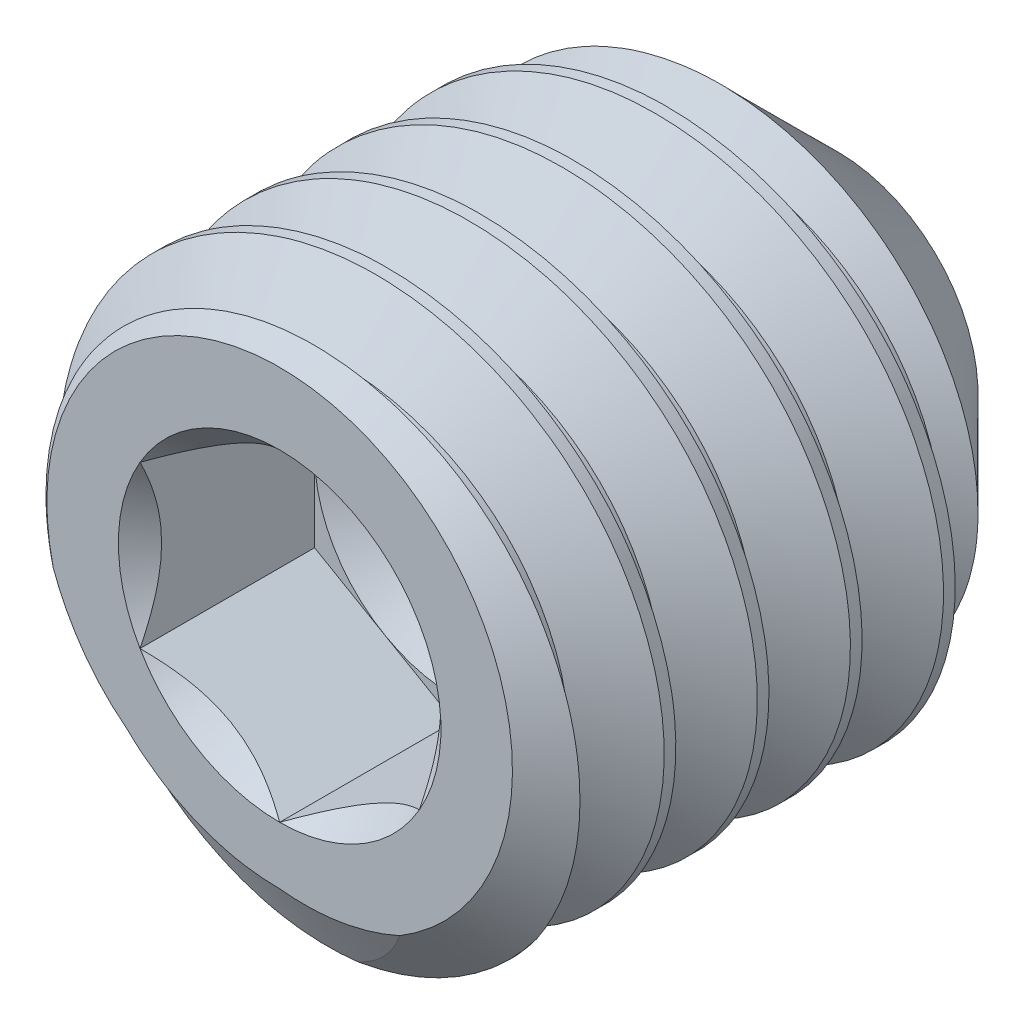
SolidWorks part; units mm, degrees
other "Imported1" parameters "D3"=3.3, "D1"=46.842, "Length"=3, "Drive Size"=1.5, "Thread Size"=3, "Thread Pitch"=0.5, "D2"=0.0866, "hex Depth"=0.9375, "Dia"=12, "D4"=2.3829, "Cup Point Dia"=3.3528, "D5"=1.436, "D6"=1.4986, "D7"=5.0014, "Pitch"=1.75
ref_plane "Front" through (0, 0, 0) normal (0, 0, 1) x (1, 0, 0)
ref_plane "Top" through (0, 0, 0) normal (0, 1, 0) x (1, 0, 0)
ref_plane "Right" through (0, 0, 0) normal (1, 0, 0) x (0, 0, -1)
sketch "Sketch1" plane through (0, 0, 0) normal (1, 0, 0) x (0, 0, -1)
  line L0 (1.5, 1.5) -> (-1.5, 1.5) construction
  line L1 (-1.5, 1.5) -> (-1.5, -1.5) construction
  line L2 (-1.5, -1.5) -> (1.5, -1.5) construction
  line L3 (1.5, -1.5) -> (1.5, 1.5) construction
  line L4 (-1.5, 0.75) -> (-1.5, -0.75) construction
  line L5 (1.4688, 1.5541) -> (1.9688, 1.5541) construction
  line L6 (1.4688, 1.5541) -> (1.5, 1.5) construction
  line L7 (1.5, 1.5) -> (1.9375, 1.5) construction
  line L8 (1.9375, 1.5) -> (1.9688, 1.5541) construction
  line L9 (1.5, 1.5) -> (1.7188, 1.1211) construction
  line L10 (1.7188, 1.1211) -> (1.9375, 1.5) construction
  line L11 (1.6875, 1.1752) -> (1.75, 1.1752) construction
  line L12 (1.7188, 1.5541) -> (1.7188, 1.5) construction
  line L13 (1.7188, 1.1752) -> (1.7188, 1.1211) construction
  point P3 (0, 1.5)
  point P24 (-1.5, 0)
  point P25 (-1.5, 0)
  dimension "D1" = 0.0625
sketch "Sketch11" plane through (0, 0, 0) normal (1, 0, 0) x (0, 0, -1)
  line L0 (-1.5, 0) -> (-1.5, 1.25)
  line L1 (-1.5, 1.25) -> (-1.3249, 1.5)
  line L2 (-1.3249, 1.5) -> (0.75, 1.5)
  line L3 (0.75, 1.5) -> (1.5, 0.75)
  line L4 (1.5, 0.75) -> (1.0494, 0)
  line L5 (1.0494, 0) -> (-1.5, 0)
  line L6 (1.0494, 0) -> (1.5, 0) construction
  line L7 (1.5, 0) -> (1.5, 0.75) construction
  line L8 (1.5, -0.75) -> (1.0494, 0) construction
  line L9 (-1.3249, -1.5) -> (0.75, -1.5) construction
  line L10 (-1.5, -1.5) -> (1.5, -1.5) construction
  line L11 (-1.5, 1.5) -> (-1.5, -1.5) construction
  line L12 (1.5, -1.5) -> (1.5, 1.5) construction
  point P11 (-0.25, -1.5)
  point P12 (-1.5, 1.5)
  dimension "D3" = 35
  dimension "D5" = 118
  dimension "D6" = 45
  dimension "D1" = 0.25
  dimension "D2" = 1.75
  dimension "D4" = 0.75
revolve "Revolve1" add sketch "Sketch11" angle 360 about L6
sketch "Sketch2" plane through (0, 0, 1.5) normal (0, 0, 1) x (1, 0, 0)
  line L1 (0, 0.866) -> (-0.75, 0.433)
  line L2 (-0.75, 0.433) -> (-0.75, -0.433)
  line L3 (-0.75, -0.433) -> (0, -0.866)
  line L4 (0, -0.866) -> (0.75, -0.433)
  line L5 (0.75, -0.433) -> (0.75, 0.433)
  line L6 (0.75, 0.433) -> (0, 0.866)
  circle A0 centre (0, 0) radius 0.75 construction
  circle A1 centre (0, 0) radius 1.5 construction
extrude "Cut-Extrude1" cut sketch "Sketch2" against normal blind 0.9375
sketch "Sketch3" plane through (0, 0, 1.5) normal (0, 0, 1) x (1, 0, 0)
  circle A0 centre (0, 0) radius 0.866
extrude "Cut-Extrude2" cut sketch "Sketch3" against normal through all draft 45
sketch "Sketch4" plane through (0, 0, 0.5625) normal (0, 0, 1) x (1, 0, 0)
  circle A0 centre (0, 0) radius 0.75 construction
  circle A1 centre (0, 0) radius 0.75
extrude "Cut-Extrude3" cut sketch "Sketch4" against normal through all draft 60
sketch "Sketch13" plane through (0, 0, 0) normal (1, 0, 0) x (0, 0, -1)
  line L0 (0, -1.5) -> (0, 1.5) construction
  line L2 (-1.3249, 1.5) -> (0.75, 1.5) construction
  line L4 (1.0494, 0) -> (-1.5, 0) construction
  point P0 (-1.9506, 0)
  point P4 (0, 0)
  point P9 (1.9506, 0)
  dimension "D1" = 3
ref_plane "Plane1" through (0, 0, -1.5) normal (0, 0, 1) x (1, 0, 0)
sketch "Sketch5" plane through (0, 0, -1.5) normal (0, 0, 1) x (1, 0, 0)
  circle A0 centre (0, 0) radius 1.5 construction
  circle A1 centre (0, 0) radius 1.5
curve "Helix/Spiral1" pitch 0.5 height 3.3 radius 1.5 centre (0, 0, -1.5) axis (0, 0, 1) start towards (0, 1, 0)
sketch "Sketch6" plane through (0, 0, 0) normal (1, 0, 0) x (0, 0, -1)
  line L0 (1.4844, 1.5271) -> (1.9531, 1.5271)
  line L1 (1.4688, 1.5541) -> (1.5, 1.5) construction
  line L2 (1.9375, 1.5) -> (1.9688, 1.5541) construction
  line L3 (1.9531, 1.5271) -> (1.75, 1.1752)
  line L4 (1.75, 1.1752) -> (1.6875, 1.1752)
  line L5 (1.6875, 1.1752) -> (1.4844, 1.5271)
sweep "Cut-Sweep1" cut profiles "Sketch6" path "Helix/Spiral1"
equation "\"D3@Helix/Spiral1\" = \"Length@Sketch1\" * 1.1"
equation "\"hex Depth@Cut-Extrude1\"=\"Drive Size@Sketch1\" * .625"
equation "\"D1@Sketch11\" = \"Thread Pitch@Sketch1\" * .5"
equation "\"D2@Sketch11\" = \"Thread Pitch@Sketch1\" * 3.5"
equation "\"D1@Helix/Spiral1\" = \"Thread Pitch@Sketch1\""
equation "\"D4@Sketch11\" = \"Thread Pitch@Sketch1\" * 1.5"
equation "\"D1@Sketch1\" = \"Thread Pitch@Sketch1\" / 8"
equation "\"D1@Sketch13\"=\"Thread Size@Sketch1\""
